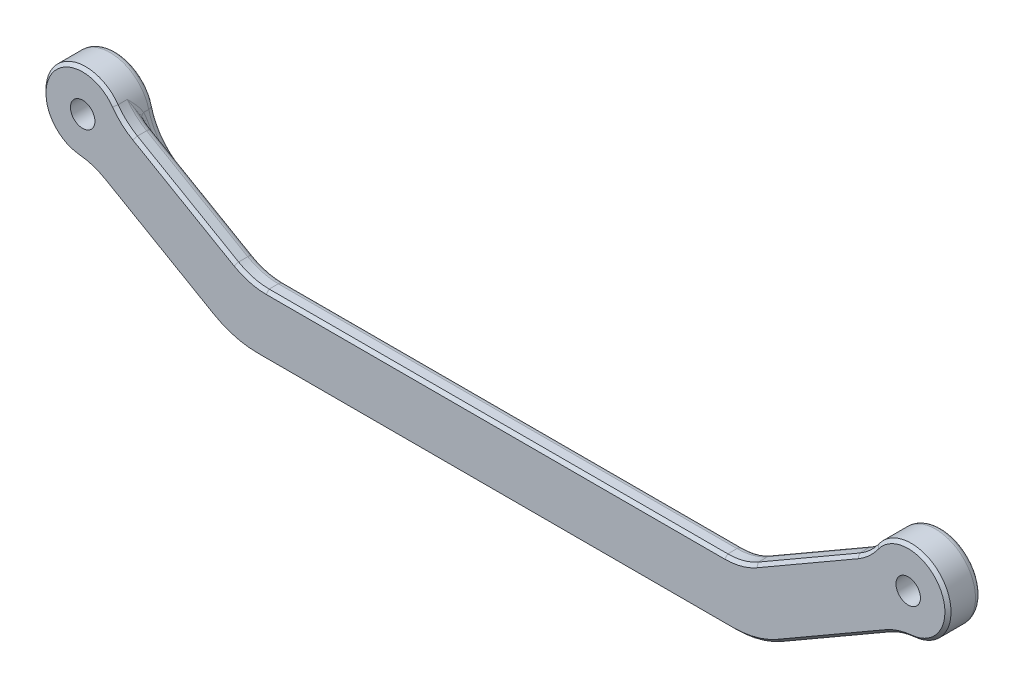
SolidWorks part; units mm, degrees
ref_plane "前视基准面" through (0, 0, 0) normal (0, 0, 1) x (1, 0, 0)
ref_plane "上视基准面" through (0, 0, 0) normal (0, 1, 0) x (1, 0, 0)
ref_plane "右视基准面" through (0, 0, 0) normal (1, 0, 0) x (0, 0, -1)
other "Configuration Table"
sketch "草图1" plane through (0, 0, 0) normal (0, 0, 1) x (1, 0, 0)
  line L0 (0, 0) -> (59.0759, 0) construction
  line L1 (37.8797, 0) -> (37.8797, 11.8481) construction
  circle A0 centre (-29.6203, 0) radius 6.5
  circle A1 centre (105.3797, 0) radius 6.5
  dimension "D1" = 13
  dimension "D2" = 135
extrude "凸台-拉伸1" add sketch "草图1" along normal blind 5.5
sketch "草图2" plane through (0, 0, 5.5) normal (0, 0, 1) x (1, 0, 0)
  line L0 (-29.6203, 0) -> (105.3797, 0) construction
  line L1 (37.8797, -33.3303) -> (37.8797, 33.3303) construction
  line L2 (-3.6395, -15) -> (79.399, -15) construction
  line L3 (-29.6203, 0) -> (-3.6395, -15) construction
  line L4 (79.399, -15) -> (105.3797, 0) construction
  line L5 (-32.1203, -4.3301) -> (-4.9792, -20)
  line L6 (-4.9792, -20) -> (80.7387, -20)
  line L7 (80.7387, -20) -> (107.8797, -4.3301)
  line L8 (-27.1203, 4.3301) -> (-2.2997, -10)
  line L9 (-2.2997, -10) -> (78.0592, -10)
  line L10 (78.0592, -10) -> (102.8797, 4.3301)
  line L11 (-27.1203, 4.3301) -> (-32.1203, -4.3301)
  line L12 (102.8797, 4.3301) -> (107.8797, -4.3301)
  point P9 (37.8797, 0)
  dimension "D1" = 15
  dimension "D2" = 30
  dimension "D3" = 30
extrude "凸台-拉伸2" add sketch "草图2" against normal blind 3
sketch "草图3" plane through (0, 0, 2.5) normal (0, 0, -1) x (-1, 0, 0)
  line L0 (-105.3797, 0) -> (-79.0546, -14.6585) construction
  line L1 (-79.0546, -14.6585) -> (4.2311, -14.6585) construction
  line L2 (4.2311, -14.6585) -> (29.6203, 0) construction
  line L3 (2.2997, -10) -> (23.5234, 2.2535) construction
  line L4 (-106.1095, -1.3105) -> (-79.4441, -16.1585)
  line L5 (-79.4441, -16.1585) -> (4.633, -16.1585)
  line L6 (4.633, -16.1585) -> (30.3703, -1.299)
  line L7 (-104.65, 1.3105) -> (-78.6652, -13.1585)
  line L8 (-78.6652, -13.1585) -> (3.8291, -13.1585)
  line L9 (3.8291, -13.1585) -> (28.8703, 1.299)
  line L10 (-104.65, 1.3105) -> (-106.1095, -1.3105)
  line L11 (28.8703, 1.299) -> (30.3703, -1.299)
extrude "凸台-拉伸3" add sketch "草图3" along normal up to surface (2.5 mm away) up to face at (98.8797, 0, 0)
sketch "草图4" plane through (0, 0, 0) normal (0, 0, -1) x (-1, 0, 0)
  circle A0 centre (-105.3797, 0) radius 2
  circle A1 centre (29.6203, 0) radius 2
  dimension "D1" = 4
  dimension "D2" = 4
extrude "切除-拉伸1" cut sketch "草图4" against normal blind 30
fillet "圆角1" radius 10 4 edges at (99.2829, 2.2535, 4) (-23.5234, 2.2535, 4) (-28.5234, -6.4068, 4) (104.2829, -6.4068, 4)
fillet "圆角2" radius 10 8 edges at (-24.893, -4.4613, 1.25) (100.5838, -4.3874, 1.25) (-23.393, -1.8632, 1.25) (99.1243, -1.7663, 1.25) (-2.2997, -10, 4) (78.0592, -10, 4) (-3.8291, -13.1585, 1.25) (78.6652, -13.1585, 1.25)
fillet "圆角3" radius 15 4 edges at (80.7387, -20, 4) (-4.9792, -20, 4) (-4.633, -16.1585, 1.25) (79.4441, -16.1585, 1.25)
fillet "圆角4" radius 1 30 edges at (98.6582, 2.1583, 2.5) (-22.8987, 2.1583, 2.5) (-12.8938, -3.8835, 2.5) (-2.2084, -9.6593, 2.5) (37.8797, -10, 2.5) (77.9679, -9.6593, 2.5) (89.3093, -10.6652, 0) (99.5564, -5.8621, 0) (111.0587, 3.1622, 0) (97.3296, -1.863, 0) (87.623, -8.1705, 0) (78.5818, -12.8375, 0) (37.4595, -13.1585, 0) (-3.7378, -12.8177, 0) (-12.3865, -8.2179, 0) (-21.6, -1.9878, 0) (-35.2494, 3.25, 0) (-23.8886, -5.9519, 0) (-14.1185, -10.682, 0) (-4.496, -15.6473, 0) (37.4679, -16.1585, 0) (-28.1286, -6.9002, 2.5) (-17.3137, -12.8787, 2.5) (-4.8423, -19.4889, 2.5) (103.8881, -6.9002, 2.5) (93.0731, -12.8787, 2.5) (80.6018, -19.4889, 2.5) (88.6533, -3.8835, 2.5) (79.3191, -15.677, 0) (37.8797, -20, 2.5)
fillet "倒角2" radius 0.5 16 edges at (77.9679, -9.6593, 5.5) (88.6533, -3.8835, 5.5) (98.6582, 2.1583, 5.5) (111.0089, 3.25, 5.5) (103.8881, -6.9002, 5.5) (93.0731, -12.8787, 5.5) (80.6018, -19.4889, 5.5) (37.8797, -20, 5.5) (-4.8423, -19.4889, 5.5) (-17.3137, -12.8787, 5.5) (-28.1286, -6.9002, 5.5) (-35.2494, 3.25, 5.5) (-22.8987, 2.1583, 5.5) (-12.8938, -3.8835, 5.5) (-2.2084, -9.6593, 5.5) (37.8797, -10, 5.5) profile chamfer
fillet "圆角5" radius 1 22 edges at (104.7363, -6.4681, 2.9036) (99.3467, -5.8872, 2.5) (89.3093, -10.6652, 2.5) (79.3191, -15.677, 2.5) (-29.1401, -6.4822, 2.9739) (-23.6205, -5.9889, 2.5) (-14.1185, -10.682, 2.5) (-4.496, -15.6473, 2.5) (-23.7664, 2.8253, 2.9739) (-21.4338, -2.2015, 2.5) (-12.3865, -8.2179, 2.5) (-3.7378, -12.8177, 2.5) (99.5997, 2.9734, 3.0481) (97.1202, -2.1221, 2.5) (87.623, -8.1705, 2.5) (78.5818, -12.8375, 2.5) (37.4679, -16.1585, 2.5) (37.4595, -13.1585, 2.5)
